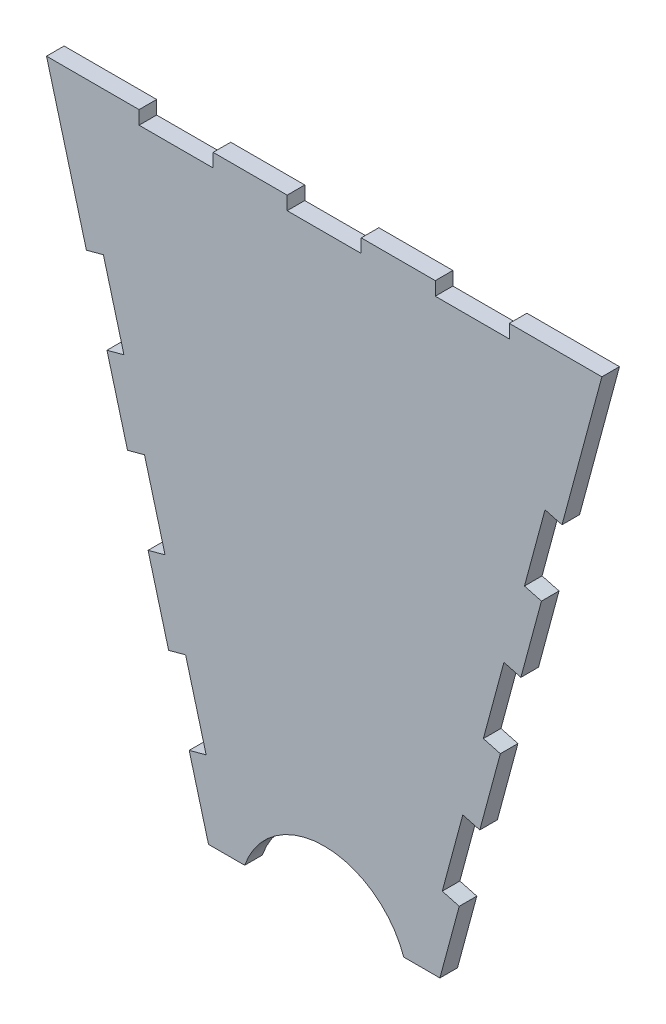
SolidWorks part; units mm, degrees
ref_plane "Front Plane" through (0, 0, 0) normal (0, 0, 1) x (1, 0, 0)
ref_plane "Top Plane" through (0, 0, 0) normal (0, 1, 0) x (1, 0, 0)
ref_plane "Right Plane" through (0, 0, 0) normal (1, 0, 0) x (0, 0, -1)
sketch "Sketch1" plane through (0, 0, 0) normal (0, 0, 1) x (1, 0, 0)
  line L0 (0, 165.1) -> (44.45, 0)
  line L1 (0, 0) -> (152.4, 0)
  line L2 (0, 0) -> (0, 165.1)
  line L3 (0, 165.1) -> (152.4, 165.1)
  line L4 (152.4, 0) -> (152.4, 165.1)
  line L6 (152.4, 165.1) -> (107.95, 0)
  dimension "D1" = 152.4
  dimension "D2" = 165.1
  dimension "D3" = 44.45
  dimension "D4" = 44.45
extrude "Boss-Extrude1" add sketch "Sketch1" along normal blind 4.826 contours L6 L3 L0 L1 region at (76.2, 93.8804, 0)
sketch "Sketch2" plane through (0, 0, 4.826) normal (0, 0, 1) x (1, 0, 0)
  line L0 (76.2, 0) -> (76.2, 165.1) construction
  line L1 (10.9436, 124.4523) -> (15.6037, 125.7069)
  line L2 (0, 165.1) -> (44.45, 0) construction
  line L3 (15.6037, 125.7069) -> (21.2444, 104.7558)
  line L4 (21.2444, 104.7558) -> (16.5843, 103.5012)
  line L5 (16.5843, 103.5012) -> (10.9436, 124.4523)
  line L6 (22.225, 82.55) -> (26.8851, 83.8046)
  line L7 (26.8851, 83.8046) -> (32.5258, 62.8535)
  line L8 (32.5258, 62.8535) -> (27.8657, 61.5988)
  line L9 (27.8657, 61.5988) -> (22.225, 82.55)
  line L10 (33.5064, 40.6477) -> (38.1665, 41.9023)
  line L11 (38.1665, 41.9023) -> (43.8072, 20.9512)
  line L12 (43.8072, 20.9512) -> (39.1471, 19.6965)
  line L13 (39.1471, 19.6965) -> (33.5064, 40.6477)
  line L14 (0, 165.1) -> (152.4, 165.1) construction
  line L16 (21.2444, 104.7558) -> (26.8851, 83.8046) construction
  line L17 (32.5258, 62.8535) -> (38.1665, 41.9023) construction
  line L18 (43.8072, 20.9512) -> (49.4478, 0) construction
  line L19 (44.45, 0) -> (107.95, 0) construction
  line L20 (108.5928, 20.9512) -> (102.9522, 0) construction
  line L21 (119.8742, 62.8535) -> (114.2335, 41.9023) construction
  line L22 (131.1556, 104.7558) -> (125.5149, 83.8046) construction
  line L23 (113.2529, 19.6965) -> (118.8936, 40.6477)
  line L24 (108.5928, 20.9512) -> (113.2529, 19.6965)
  line L25 (114.2335, 41.9023) -> (108.5928, 20.9512)
  line L26 (118.8936, 40.6477) -> (114.2335, 41.9023)
  line L27 (124.5343, 61.5988) -> (130.175, 82.55)
  line L28 (119.8742, 62.8535) -> (124.5343, 61.5988)
  line L29 (125.5149, 83.8046) -> (119.8742, 62.8535)
  line L30 (130.175, 82.55) -> (125.5149, 83.8046)
  line L31 (135.8157, 103.5012) -> (141.4564, 124.4523)
  line L32 (131.1556, 104.7558) -> (135.8157, 103.5012)
  line L33 (136.7963, 125.7069) -> (131.1556, 104.7558)
  line L34 (141.4564, 124.4523) -> (136.7963, 125.7069)
  line L35 (43.8072, 20.9512) -> (49.4478, 0) construction
  dimension "D1" = 4.826
extrude "Cut-Extrude1" cut sketch "Sketch2" against normal through all
sketch "Sketch3" plane through (0, 0, 4.826) normal (0, 0, 1) x (1, 0, 0)
  line L2 (0, 165.1) -> (152.4, 165.1) construction
  circle A0 centre (76.2, -7.62) radius 23.114
  dimension "D1" = 46.228
  dimension "D2" = 172.72
extrude "Cut-Extrude2" cut sketch "Sketch3" against normal blind 4.826
sketch "Sketch4" plane through (0, 0, 4.826) normal (0, 0, 1) x (1, 0, 0)
  line L0 (127, 167.9001) -> (127, 163.2817) construction
  line L1 (127, 163.2817) -> (106.68, 163.2817) construction
  line L2 (127, 167.9001) -> (106.68, 167.9001) construction
  line L3 (106.68, 167.9001) -> (106.68, 163.2817) construction
  line L4 (86.36, 163.2817) -> (66.04, 163.2817) construction
  line L5 (66.04, 167.9001) -> (66.04, 163.2817) construction
  line L6 (86.36, 167.9001) -> (66.04, 167.9001) construction
  line L7 (86.36, 167.9001) -> (86.36, 163.2817) construction
  line L8 (45.72, 163.2817) -> (25.4, 163.2817) construction
  line L9 (45.72, 167.9001) -> (45.72, 163.2817) construction
  line L10 (45.72, 167.9001) -> (25.4, 167.9001) construction
  line L11 (25.4, 167.9001) -> (25.4, 163.2817) construction
  line L12 (127, 167.9001) -> (127, 163.2817)
  line L13 (127, 163.2817) -> (106.68, 163.2817)
  line L14 (127, 167.9001) -> (106.68, 167.9001)
  line L15 (106.68, 167.9001) -> (106.68, 163.2817)
  line L16 (86.36, 163.2817) -> (66.04, 163.2817)
  line L17 (66.04, 167.9001) -> (66.04, 163.2817)
  line L18 (86.36, 167.9001) -> (66.04, 167.9001)
  line L19 (86.36, 167.9001) -> (86.36, 163.2817)
  line L20 (45.72, 163.2817) -> (25.4, 163.2817)
  line L21 (45.72, 167.9001) -> (45.72, 163.2817)
  line L22 (45.72, 167.9001) -> (25.4, 167.9001)
  line L23 (25.4, 167.9001) -> (25.4, 163.2817)
extrude "Cut-Extrude3" cut sketch "Sketch4" against normal through all
sketch "Sketch5" plane through (0, 0, 4.826) normal (0, 0, 1) x (1, 0, 0)
  line L1 (127, 163.2817) -> (106.68, 163.2817)
  line L2 (127, 163.2817) -> (127, 161.3905)
  line L3 (127, 161.3905) -> (106.68, 161.3905)
  line L4 (106.68, 163.2817) -> (106.68, 161.3905)
  line L5 (86.36, 163.2817) -> (66.04, 163.2817)
  line L6 (86.36, 163.2817) -> (86.36, 161.3905)
  line L7 (86.36, 161.3905) -> (66.04, 161.3905)
  line L8 (66.04, 163.2817) -> (66.04, 161.3905)
  line L9 (45.72, 163.2817) -> (25.4, 163.2817)
  line L10 (45.72, 163.2817) -> (45.72, 161.3905)
  line L11 (45.72, 161.3905) -> (25.4, 161.3905)
  line L12 (25.4, 163.2817) -> (25.4, 161.3905)
extrude "Cut-Extrude4" cut sketch "Sketch5" against normal through all
equation "\"MDF\"= 0.19in"
equation "\"PVCID\" = 2.067in"
equation "\"PVCOD\" = 2.375in"
equation "\"GenDiameter\"= 60mm"
equation "\"GenCutDiameter\" = 1.8in"
equation "\"GenCutDistance\" = 1"
equation "\"TowerHeight\" = 6in"
equation "\"TowerFrontBase\" = 3in"
equation "\"FunnelHeight\" = 1in"
equation "\"FunnelAngle\" = 20"
equation "\"TowerSideBase\" = 3in"
equation "\"TowerPanelLength\" = 2in"
equation "\"TowerPanelLeeway\" = 0.5in"
equation "\"BaseLength\" = 9in"
equation "\"BaseWidth\" = 10in"
equation "\"WheelHoleLength\" = 3.25in"
equation "\"WheelHoleWidth\" = 26mm"
equation "\"WheelHoleFromBack\" = 1.5in"
equation "\"DropLength\" = 1in"
equation "\"DropWidth\" = 8.5in"
equation "\"BumperWidth\" = 2in"
equation "\"SmallHexDiameter\" = 0.185in"
equation "\"SmallHexHeight\" = 0.701in"
equation "\"ScrewSize\" = 0.106in"
equation "\"BigHexDiameter\" = 0.251in"
equation "\"BigHexHeight\" = 0.374in"
equation "\"PCBThickness\" = 0.066in"
equation "\"ConnectorHeight\" = 0.517in"
equation "\"BoardHeight\" = 0.583in"
equation "\"UnoStackHeight\" = 1.351in"
equation "\"UnoStackWidth\" = 3.053in"
equation "\"UnoStackLength\" = 3.152in"
equation "\"HBridgeWidth\" = 1.797in"
equation "\"HBridgeLength\" = 2.236in"
equation "\"DSWidth\" = 1.820in"
equation "\"DSLength\" = 1.833in"
equation "\"StepperWidth\" = 1.799in"
equation "\"StepperLength\" = 2.248in"
equation "\"ULNWidth\" = 1.304in"
equation "\"ULNLength\" = 1.545in"
equation "\"VSwitchHeight\" = 0.392in"
equation "\"VSwitchWidth\" = 0.637in"
equation "\"VSwitchLength\" = 1.097in"
equation "\"SkateWheelDiameter\" = 80mm"
equation "\"SkateWheelThickness\" = 24mm"
equation "\"BaseDistance\" = 3in"
equation "\"DummyVar\" = 2in"
equation "\"D1@Boss-Extrude1\"=\"MDF\""
equation "\"D1@Sketch2\"=\"MDF\""
equation "\"D1@Cut-Extrude2\"=\"MDF\""
